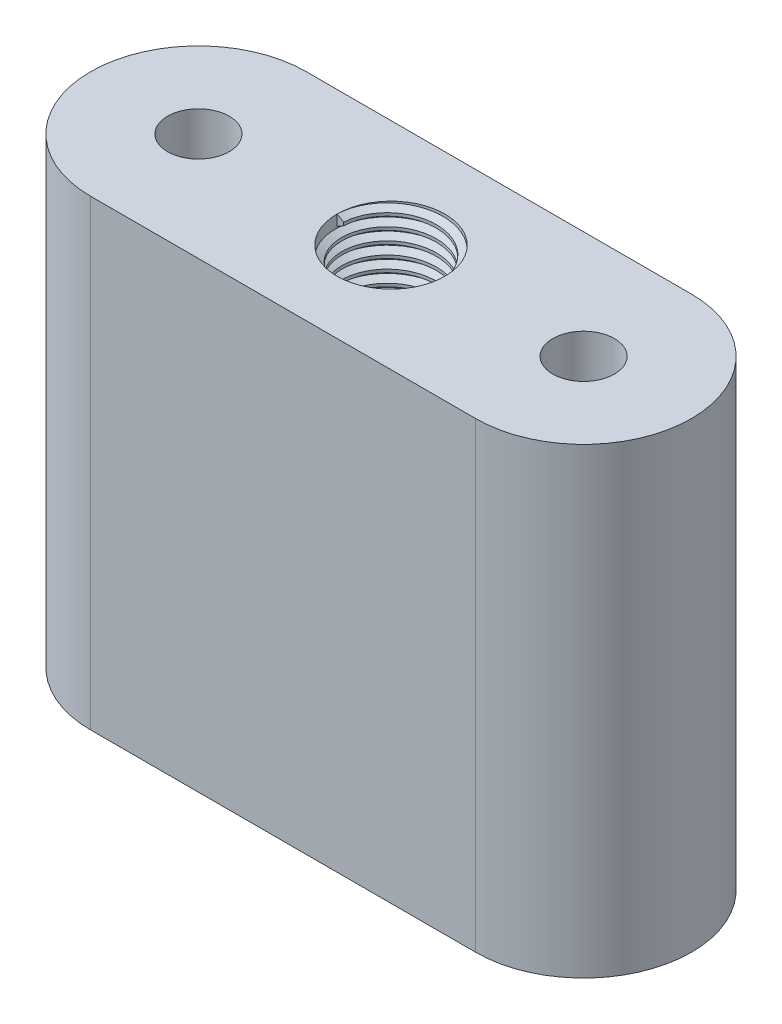
SolidWorks part; units mm, degrees
ref_plane "Front Plane" through (0, 0, 0) normal (0, 0, 1) x (1, 0, 0)
ref_plane "Top Plane" through (0, 0, 0) normal (0, 1, 0) x (1, 0, 0)
ref_plane "Right Plane" through (0, 0, 0) normal (1, 0, 0) x (0, 0, -1)
sketch "Sketch2" plane through (0, 0, 0) normal (0, 1, 0) x (1, 0, 0)
  line L0 (0, 0) -> (-25, 0) construction
  line L1 (0, -7) -> (-25, -7)
  line L2 (0, 7) -> (-25, 7)
  arc A0 (0, -7) -> (0, 7) centre (0, 0) ccw
  arc A1 (-25, 7) -> (-25, -7) centre (-25, 0) ccw
  circle A2 centre (0, 0) radius 2
  circle A3 centre (-25, 0) radius 2
  point P3 (-12.5, 0)
  dimension "D2" = 7
  dimension "D3" = 4
  dimension "D4" = 4
  dimension "D1" = 25
extrude "Boss-Extrude2" add sketch "Sketch2" against normal blind 30
sketch "Sketch5" plane through (0, 0, 0) normal (0, 1, 0) x (1, 0, 0)
  line L0 (-32, 0) -> (7, 0) construction
  arc A0 (-25, 7) -> (-25, -7) centre (-25, 0) ccw construction
  arc A1 (0, -7) -> (0, 7) centre (0, 0) ccw construction
  circle A2 centre (-12.5, 0) radius 2.9045
hole_wizard "M8x1.0 Tapped Hole1" positions "Sketch6" profile "Sketch7" tap size "M8x1.0" standard "ANSI Metric"
sketch "Sketch6" plane through (0, 0, 0) normal (0, 1, 0) x (1, 0, 0)
  point P0 (-12.5, 0)
sketch "Sketch7" plane through (-12.5, 0, 0) normal (1, 0, 0) x (0, 0, 1)
  line L0 (0, 0) -> (0, 20)
  line L1 (0, 20) -> (3.5, 17.897)
  line L2 (3.5, 17.897) -> (3.5, 0)
  line L5 (3.5, 0) -> (0, 0)
  line L10 (0, 20) -> (-3.5, 17.897) construction
  line L11 (0, -6.35) -> (0, 107.95) construction
  dimension "Tap Drill Dia." = 7
  dimension "Tap Drill Depth" = 20
  dimension "Drill Angle" = 118
cosmetic thread "Hole Thread1" parameters "D1"=16, "D2"=8
thread "Thread1" pitch 0.7937 method extrude profile "Thread Profile1" start angle 0, offset 0, length 16, pitch 0.7937, diameter 7
ref_plane "Plane1" through (-16, 0, 0) normal (0, 0, 1) x (-1, 0, 0)
sketch "Thread Profile1" plane through (-16, 0, 0) normal (0, 0, 1) x (-1, 0, 0)
  line L0 (0, 0) -> (0, 0.7937) construction
  line L11 (0, 0) -> (0, 0.6945)
  line L12 (0, 0.6945) -> (-0.4296, 0.4465)
  line L13 (-0.4296, 0.4465) -> (-0.4296, 0.248)
  line L15 (-0.4296, 0.248) -> (0, 0)
  line L17 (-0.4296, 0.3473) -> (0, 0.3473) construction
  point P2 (0, 0)
  dimension "Pitch" = 0.7937
  dimension "Profile_Angle" = 60
  dimension "Profile_Land" = 0.1984
  dimension "Profile_Height" = 0.4296
